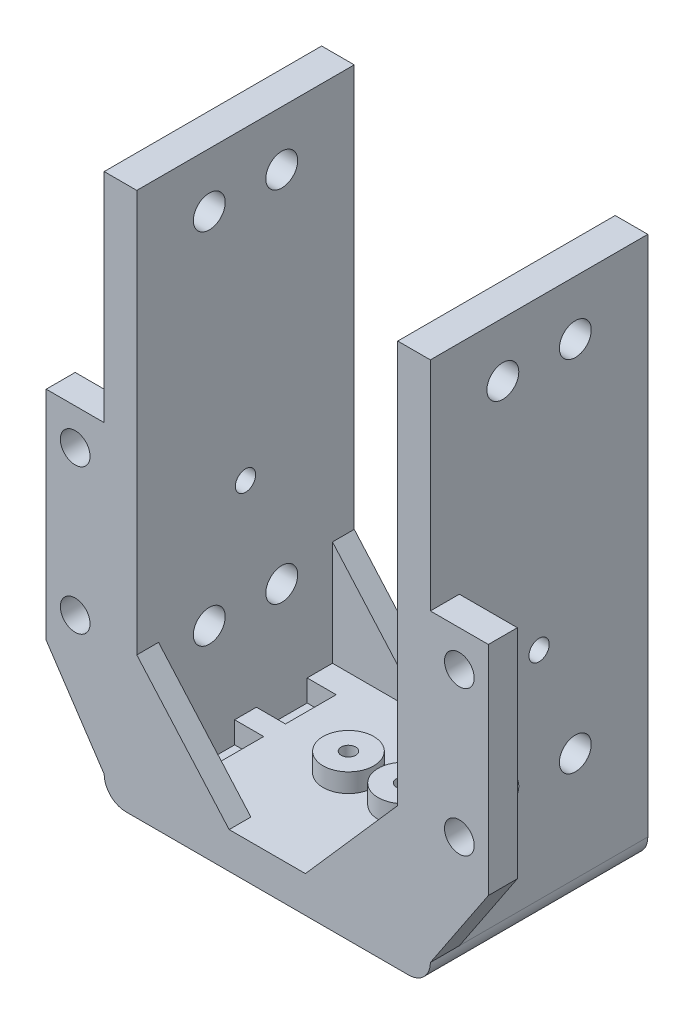
SolidWorks part; units mm, degrees
ref_plane "Front Plane" through (0, 0, 0) normal (0, 0, 1) x (1, 0, 0)
ref_plane "Top Plane" through (0, 0, 0) normal (0, 1, 0) x (1, 0, 0)
ref_plane "Right Plane" through (0, 0, 0) normal (1, 0, 0) x (0, 0, -1)
sketch "Sketch1" plane through (0, 0, 0) normal (0, 1, 0) x (1, 0, 0)
  line L1 (-22.5, 15) -> (22.5, 15)
  line L2 (-22.5, 15) -> (-22.5, -15)
  line L3 (-22.5, -15) -> (22.5, -15)
  line L4 (22.5, 15) -> (22.5, -15)
  line L5 (-22.5, 15) -> (22.5, -15) construction
  line L6 (-22.5, -15) -> (22.5, 15) construction
  circle A0 centre (-3.8, 0) radius 1
  circle A1 centre (3.8, 0) radius 1
  circle A2 centre (-3.8, 0) radius 3.5
  circle A3 centre (3.8, 0) radius 3.5
  point P0 (0, 0)
  dimension "D5" = 2
  dimension "D6" = 2
  dimension "D7" = 7
  dimension "D1" = 30
  dimension "D2" = 45
  dimension "D3" = 7.6
  dimension "D4" = 3.8
extrude "Boss-Extrude1" add sketch "Sketch1" along normal blind 5 contours L4 L1 L2 L3 A3 A2 region at (0, 0, 0)
extrude "Boss-Extrude2" add sketch "Sketch1<4>" along normal blind 7.6 contours A3 A1 | A2 A0 region at (-7.201, 0, 0) region at (0.399, 0, 0)
sketch "Sketch1<4>" plane through (0, 0, 0) normal (0, 1, 0) x (1, 0, 0) same geometry as "Sketch1"
sketch "Sketch2" plane through (0, 5, 0) normal (0, 1, 0) x (1, 0, 0)
  line L0 (-22.5, -15) -> (22.5, -15) construction
  line L1 (-22.5, 15) -> (-18, 15)
  line L2 (-22.5, 15) -> (-22.5, -15)
  line L3 (-22.5, -15) -> (-18, -15)
  line L4 (-18, 15) -> (-18, -15)
  line L6 (22.5, 15) -> (18, 15)
  line L7 (22.5, 15) -> (22.5, -15)
  line L8 (22.5, -15) -> (18, -15)
  line L9 (18, 15) -> (18, -15)
  dimension "D1" = 4.5
  dimension "D2" = 4.5
extrude "Boss-Extrude3" add sketch "Sketch2" along normal blind 70
sketch "Sketch3" plane through (-22.5, 0, 0) normal (-1, 0, 0) x (0, 0, 1)
  line L0 (0, 75) -> (0, 0) construction
  line L1 (-15, 0) -> (15, 0) construction
  line L2 (15, 75) -> (-15, 75) construction
  circle A0 centre (0, 32.83) radius 1.4
  circle A1 centre (5, 17.98) radius 2.2
  circle A2 centre (-5, 17.98) radius 2.2
  circle A3 centre (-5, 67.48) radius 2.2
  circle A4 centre (5, 67.48) radius 2.2
  dimension "D1" = 32.83
  dimension "D4" = 4.4
  dimension "D5" = 4.4
  dimension "D7" = 4.4
  dimension "D9" = 2.8
  dimension "D2" = 5
  dimension "D3" = 10
  dimension "D6" = 49.5
  dimension "D8" = 10
  dimension "D11" = 34.65
  dimension "D12" = 49.5
extrude "Cut-Extrude1" cut sketch "Sketch3" against normal blind 4.5
fillet "Fillet1" radius 3 2 edges at (22.5, 0, 0) (-22.5, 0, 0)
sketch "Sketch6" plane through (0, 5, 0) normal (0, 1, 0) x (1, 0, 0)
  line L0 (-18, -15) -> (-18, 15) construction
  line L1 (-18, 8.5) -> (-13.9918, 8.5)
  line L2 (-18, 8.5) -> (-18, 1.5)
  line L3 (-18, 1.5) -> (-13.9918, 1.5)
  line L4 (-13.9918, 8.5) -> (-13.9918, 1.5)
  line L5 (-18, 15) -> (18, 15) construction
  line L6 (-18, -1.4) -> (18, -1.4) construction
  line L7 (18, 15) -> (18, -15) construction
  line L8 (-18, -15) -> (-18, 15) construction
  line L9 (-18, -8.5) -> (-13.9918, -8.5)
  line L10 (-18, -8.5) -> (-18, -1.5)
  line L11 (-18, -1.5) -> (-13.9918, -1.5)
  line L12 (-13.9918, -8.5) -> (-13.9918, -1.5)
  line L13 (-18, -15) -> (18, -15) construction
  dimension "D1" = 6.5
  dimension "D2" = 13.5
  dimension "D3" = 6.5
  dimension "D4" = 13.5
extrude "Cut-Extrude3" cut sketch "Sketch6" against normal blind 3
mirror "Mirror1" about plane through (0, 0, 0) normal (1, 0, 0) of "Cut-Extrude1", "Cut-Extrude3"
sketch "Sketch7" plane through (0, 0, 15) normal (0, 0, 1) x (1, 0, 0)
  line L0 (-18, 19.5) -> (-5.2592, 5)
  line L1 (-18, 75) -> (-18, 5) construction
  line L2 (-18, 5) -> (18, 5) construction
  line L3 (-5.2592, 5) -> (-18, 5)
  line L4 (-18, 5) -> (-18, 19.5)
  line L5 (18, 75) -> (18, 5) construction
  line L7 (5.26, 5) -> (18, 5)
  line L8 (18, 19.5) -> (5.26, 5)
  line L9 (18, 5) -> (18, 19.5)
  dimension "D1" = 5.2592
  dimension "D2" = 5.26
  dimension "D3" = 14.5
  dimension "D4" = 14.5
extrude "Boss-Extrude4" add sketch "Sketch7" against normal blind 3
mirror "Mirror2" about plane through (0, 0, 0) normal (0, 0, 1) of "Boss-Extrude4"
sketch "Sketch8" plane through (0, 0, 15) normal (0, 0, 1) x (1, 0, 0)
  line L0 (-22.5, 75) -> (-22.5, 3) construction
  line L1 (0, 0) -> (0, 60.969) construction
  line L2 (-22.5, 15) -> (-22.5, 45)
  line L3 (-22.5, 45) -> (-30.5, 45)
  line L4 (-30.5, 15) -> (-30.5, 45)
  line L5 (-19.5, 0) -> (19.5, 0) construction
  line L6 (-22.5, 3) -> (-22.5, 15)
  line L7 (-26.5, 45) -> (-26.5, 15) construction
  line L8 (-30.5, 15) -> (-22.5, 3)
  line L9 (26.5, 45) -> (26.5, 15) construction
  line L10 (30.5, 15) -> (22.5, 3)
  line L11 (22.5, 3) -> (22.5, 15)
  line L12 (30.5, 15) -> (30.5, 45)
  line L13 (22.5, 45) -> (30.5, 45)
  line L14 (22.5, 15) -> (22.5, 45)
  circle A0 centre (-26.5, 40) radius 2.05
  circle A1 centre (-26.5, 20) radius 2.05
  circle A2 centre (26.5, 20) radius 2.05
  circle A3 centre (26.5, 40) radius 2.05
  point P14 (-26.5, 30)
  dimension "D3" = 20
  dimension "D1" = 4.1
  dimension "D2" = 30
  dimension "D4" = 10
  dimension "D5" = 8
extrude "Boss-Extrude5" add sketch "Sketch8" against normal blind 4
